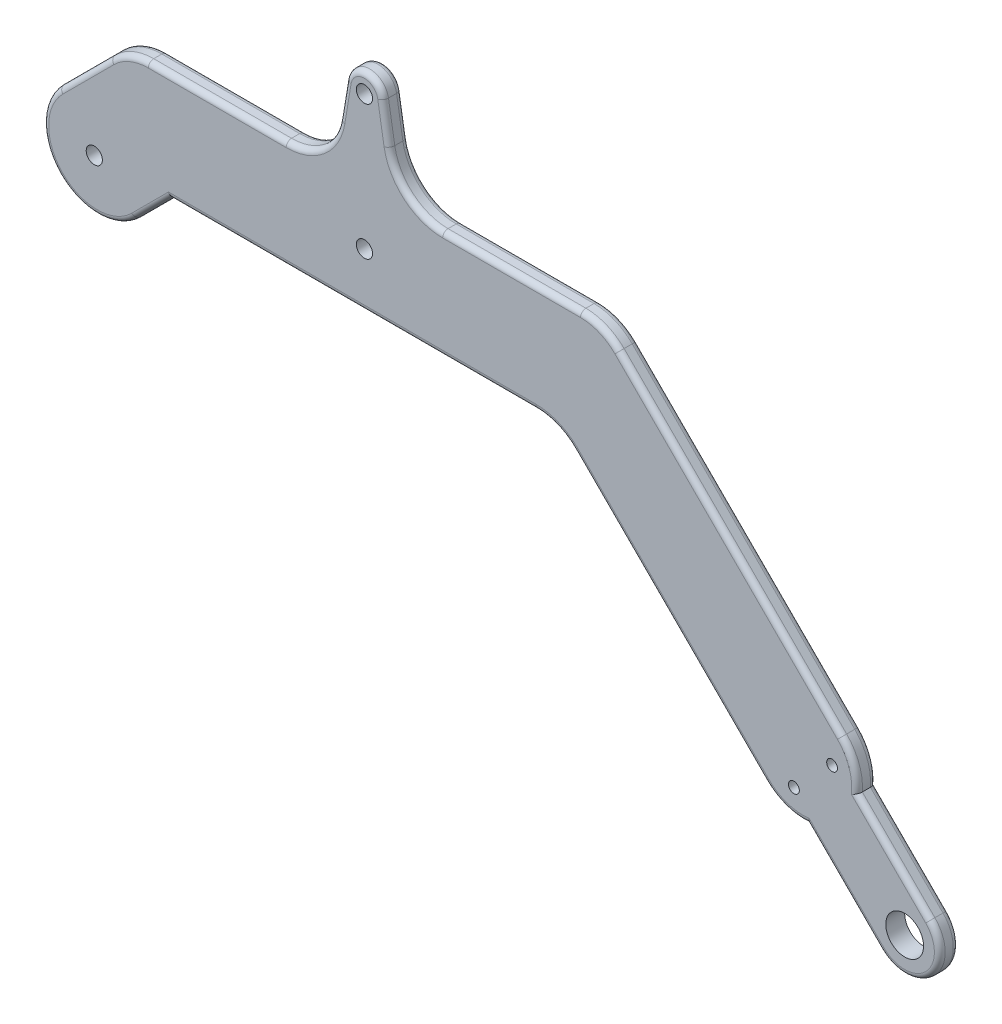
SolidWorks part; units mm, degrees
ref_plane "Front Plane" through (0, 0, 0) normal (0, 0, 1) x (1, 0, 0)
ref_plane "Top Plane" through (0, 0, 0) normal (0, 1, 0) x (1, 0, 0)
ref_plane "Right Plane" through (0, 0, 0) normal (1, 0, 0) x (0, 0, -1)
sketch "Sketch1" plane through (0, 0, 0) normal (0, 0, 1) x (1, 0, 0)
  line L0 (-100, 0) -> (100, 0) construction
  line L1 (-100, 0) -> (0, 100) construction
  line L2 (0, 100) -> (100, 0) construction
  line L3 (0, 0) -> (-50, 50) construction
  line L4 (-40, 60) -> (40, 60) construction
  line L5 (0, 100) -> (0, 60) construction
  circle A0 centre (-100, 0) radius 20
  circle A1 centre (0, 0) radius 20
  circle A2 centre (100, 0) radius 20
  point P2 (0, 0)
  dimension "D5" = 40
  dimension "D1" = 200
  dimension "D2" = 90
  dimension "D3" = 90
  dimension "D4" = 80
sketch "Sketch2" plane through (0, 0, 0) normal (0, 0, 1) x (1, 0, 0)
  line L0 (-56.5165, 43.4835) -> (-40, 60) construction
  line L1 (-100, 0) -> (0, 100) construction
  line L2 (-40, 60) -> (40, 60) construction
  line L3 (40, 60) -> (86.565, 13.435) construction
  line L4 (0, 100) -> (100, 0) construction
  line L5 (-49.4454, 36.4124) -> (-35.8579, 50)
  line L6 (-35.8579, 50) -> (35.8579, 50)
  line L7 (35.8579, 50) -> (79.4939, 6.364)
  line L8 (-63.5876, 50.5546) -> (-44.1421, 70)
  line L9 (-44.1421, 70) -> (44.1421, 70)
  line L10 (44.1421, 70) -> (93.636, 20.5061)
  line L11 (-63.5876, 50.5546) -> (-49.4454, 36.4124)
  line L12 (93.636, 20.5061) -> (79.4939, 6.364)
  line L13 (81.9688, 8.8388) -> (95.4038, -4.5962)
  line L14 (91.1612, 18.0312) -> (104.5962, 4.5962)
  line L15 (90.1005, 24.0416) -> (75.9584, 9.8995) construction
  line L16 (0, 100) -> (0, 60) construction
  line L17 (-6, 70) -> (-3.4532, 85.4203)
  line L18 (6, 70) -> (3.4532, 85.4203)
  circle A0 centre (100, 0) radius 10 construction
  circle A1 centre (100, 0) radius 3.5
  arc A2 (95.4038, -4.5962) -> (104.5962, 4.5962) centre (100, 0) ccw
  circle A3 centre (100, 0) radius 0.5
  circle A4 centre (100, 0) radius 6.5 construction
  circle A5 centre (79.4939, 13.435) radius 1
  circle A6 centre (86.565, 20.5061) radius 1
  circle A7 centre (0, 60) radius 1.5
  circle A8 centre (0, 84.85) radius 1.5
  circle A9 centre (0, 84.85) radius 3.5
  circle A10 centre (-50, 50) radius 1.5
  dimension "D4" = 20
  dimension "D5" = 7
  dimension "D12" = 2
  dimension "D13" = 3
  dimension "D18" = 3
  dimension "D3" = 27.5
  dimension "D8" = 19
  dimension "D9" = 5
  dimension "D10" = 5
  dimension "D11" = 5
  dimension "D14" = 14.85
  dimension "D16" = 6
  dimension "D17" = 6
  dimension "D1" = 10
  dimension "D2" = 10
  dimension "D6" = 3
  dimension "D7" = 3
  dimension "D15" = 2
sketch "Sketch3" plane through (0, 0, 0) normal (0, 0, 1) x (1, 0, 0)
  line L0 (-100, 0) -> (100, 0) construction
  line L1 (-86.565, 13.435) -> (-50, 50) construction
  line L2 (-100, 0) -> (0, 100) construction
  line L3 (-50, 50) -> (-13.435, 13.435) construction
  line L4 (0, 0) -> (-50, 50) construction
  line L5 (-79.4939, 6.364) -> (-50, 35.8579)
  line L6 (-50, 35.8579) -> (-20.5061, 6.364)
  line L7 (-93.636, 20.5061) -> (-50, 64.1421)
  line L8 (-50, 64.1421) -> (-6.364, 20.5061)
  line L9 (-93.636, 20.5061) -> (-79.4939, 6.364)
  line L10 (-20.5061, 6.364) -> (-6.364, 20.5061)
  line L11 (-91.1612, 18.0312) -> (-104.5962, 4.5962)
  line L12 (-81.9688, 8.8388) -> (-95.4038, -4.5962)
  line L13 (-18.0312, 8.8388) -> (-4.5962, -4.5962)
  line L14 (-8.8388, 18.0312) -> (4.5962, 4.5962)
  line L15 (-90.1005, 24.0416) -> (-75.9584, 9.8995) construction
  line L16 (-9.8995, 24.0416) -> (-24.0416, 9.8995) construction
  circle A0 centre (-100, 0) radius 3.5
  circle A1 centre (0, 0) radius 3.5
  circle A2 centre (-100, 0) radius 10 construction
  circle A3 centre (0, 0) radius 10 construction
  circle A4 centre (-100, 0) radius 6.5
  circle A5 centre (0, 0) radius 6.5
  circle A6 centre (-86.565, 20.5061) radius 1
  circle A7 centre (-79.4939, 13.435) radius 1
  circle A8 centre (-20.5061, 13.435) radius 1
  circle A9 centre (-13.435, 20.5061) radius 1
  circle A10 centre (-50, 50) radius 1.5 construction
  circle A11 centre (-50, 50) radius 1.5
  dimension "D1" = 20
  dimension "D2" = 7
  dimension "D8" = 2
  dimension "D11" = 5
  dimension "D12" = 5
  dimension "D13" = 5
  dimension "D14" = 5
  dimension "D6" = 19
  dimension "D7" = 19
  dimension "D9" = 5
  dimension "D10" = 5
  dimension "D3" = 3
  dimension "D4" = 10
  dimension "D5" = 10
sketch "Sketch4" plane through (0, 0, 0) normal (0, 0, 1) x (1, 0, 0)
  line L0 (-44.1421, 70) -> (44.1421, 70)
  line L1 (44.1421, 70) -> (57.5, 84.85)
  line L2 (57.5, 84.85) -> (57.5, 94.85)
  line L3 (57.5, 94.85) -> (-57.5, 94.85)
  line L4 (-57.5, 94.85) -> (-57.5, 84.85)
  line L5 (-57.5, 84.85) -> (-44.1421, 70)
  line L6 (-4, 60) -> (-4, 70)
  line L7 (4, 60) -> (4, 70)
  line L8 (-22.5, 86.35) -> (22.5, 86.35) construction
  line L9 (-22.5, 90.85) -> (22.5, 90.85)
  line L10 (-22.5, 81.85) -> (22.5, 81.85)
  circle A0 centre (0, 60) radius 1.5 construction
  circle A1 centre (0, 60) radius 1.5
  arc A2 (-4, 60) -> (4, 60) centre (0, 60) ccw
  circle A3 centre (0, 60) radius 4 construction
  arc A4 (-22.5, 90.85) -> (-22.5, 81.85) centre (-22.5, 86.35) ccw
  arc A5 (22.5, 81.85) -> (22.5, 90.85) centre (22.5, 86.35) ccw
  point P4 (0, 94.85)
  point P22 (0, 86.35)
  dimension "D1" = 115
  dimension "D2" = 10
  dimension "D3" = 2.5
  dimension "D4" = 45
  dimension "D5" = 9
  dimension "D6" = 4
sketch "Sketch5" plane through (0, 0, 0) normal (0, 0, 1) x (1, 0, 0)
  line L0 (81.9688, 8.8388) -> (95.4038, -4.5962) construction
  line L1 (91.1612, 18.0312) -> (104.5962, 4.5962) construction
  line L2 (6, 70) -> (3.4532, 85.4203) construction
  line L3 (-6, 70) -> (-3.4532, 85.4203) construction
  line L4 (81.9688, 8.8388) -> (95.4038, -4.5962)
  line L5 (91.1612, 18.0312) -> (104.5962, 4.5962)
  line L6 (6, 70) -> (3.4532, 85.4203)
  line L7 (-6, 70) -> (-3.4532, 85.4203)
  line L8 (93.636, 20.5061) -> (44.1421, 70)
  line L9 (79.4939, 6.364) -> (93.636, 20.5061)
  line L10 (35.8579, 50) -> (79.4939, 6.364)
  line L11 (-35.8579, 50) -> (35.8579, 50)
  line L12 (-49.4454, 36.4124) -> (-35.8579, 50)
  line L13 (-63.5876, 50.5546) -> (-49.4454, 36.4124)
  line L14 (-44.1421, 70) -> (-63.5876, 50.5546)
  line L15 (44.1421, 70) -> (-44.1421, 70)
  line L16 (93.636, 20.5061) -> (44.1421, 70)
  line L17 (79.4939, 6.364) -> (81.9688, 8.8388)
  line L18 (35.8579, 50) -> (79.4939, 6.364)
  line L19 (-35.8579, 50) -> (35.8579, 50)
  line L20 (-49.4454, 36.4124) -> (-35.8579, 50)
  line L21 (-63.5876, 50.5546) -> (-49.4454, 36.4124)
  line L22 (-44.1421, 70) -> (-63.5876, 50.5546)
  line L23 (44.1421, 70) -> (6, 70)
  line L24 (-6, 70) -> (-44.1421, 70)
  line L25 (91.1612, 18.0312) -> (93.636, 20.5061)
  arc A0 (95.4038, -4.5962) -> (104.5962, 4.5962) centre (100, 0) ccw construction
  circle A1 centre (79.4939, 13.435) radius 1
  circle A2 centre (79.4939, 13.435) radius 1
  circle A3 centre (100, 0) radius 0.5
  circle A4 centre (100, 0) radius 0.5
  circle A5 centre (100, 0) radius 3.5
  circle A6 centre (100, 0) radius 3.5
  circle A7 centre (0, 84.85) radius 3.5
  arc A8 (3.4532, 85.4203) -> (-3.4532, 85.4203) centre (0, 84.85) ccw
  circle A9 centre (0, 84.85) radius 1.5
  circle A10 centre (0, 84.85) radius 1.5
  circle A11 centre (0, 60) radius 1.5
  circle A12 centre (0, 60) radius 1.5
  circle A13 centre (86.565, 20.5061) radius 1
  circle A14 centre (86.565, 20.5061) radius 1
  circle A15 centre (-50, 50) radius 1.5
  circle A16 centre (-50, 50) radius 1.5
  arc A17 (95.4038, -4.5962) -> (104.5962, 4.5962) centre (100, 0) ccw
  dimension "D1" = 0
  dimension "D2" = 0
  dimension "D3" = 0
  dimension "D4" = 0
  dimension "D5" = 0
  dimension "D6" = 0
  dimension "D7" = 0
  dimension "D8" = 0
  dimension "D9" = 0
extrude "Boss-Extrude1" add sketch "Sketch5" along normal blind 3.5 contours L4 A17 L5 L25 L16 L23 L6 A8 L7 L24 L22 L21 L20 L19 L18 L17 A2 A6 A10 A12 A14 A16 region at (94.4348, 5.5652, 0) region at (18.0255, 50.1428, 0) region at (0, 75.758, 0) region at (3.3896, 85.128, 0)
fillet "Fillet1" radius 10 9 edges at (79.4939, 6.364, 1.75) (93.636, 20.5061, 1.75) (35.8579, 50, 1.75) (44.1421, 70, 1.75) (6, 70, 1.75) (-6, 70, 1.75) (-44.1421, 70, 1.75) (-49.4454, 36.4124, 1.75) (-63.5876, 50.5546, 1.75)
fillet "Fillet2" radius 1 44 edges at (97.8787, 11.3137, 0) (104.5962, -4.5962, 0) (77.7268, 9.4279, 0) (56.4536, 29.4043, 0) (35.5426, 49.2388, 0) (90.5721, 22.2732, 0) (67.6668, 46.4754, 0) (43.8268, 69.2388, 0) (27.2419, 70, 0) (8.0145, 72.3745, 0) (4.0354, 81.8954, 0) (-39.1161, 46.7417, 0) (-49.4454, 40.5546, 0) (-59.4454, 50.5546, 0) (-51.7938, 62.3483, 0) (-43.8268, 69.2388, 0) (-27.2419, 70, 0) (-8.0145, 72.3745, 0) (-4.0354, 81.8954, 0) (97.8787, 11.3137, 3.5) (104.5962, -4.5962, 3.5) (77.7268, 9.4279, 3.5) (56.4536, 29.4043, 3.5) (35.5426, 49.2388, 3.5) (90.5721, 22.2732, 3.5) (67.6668, 46.4754, 3.5) (43.8268, 69.2388, 3.5) (27.2419, 70, 3.5) (8.0145, 72.3745, 3.5) (4.0354, 81.8954, 3.5) (0, 88.35, 3.5) (-4.0354, 81.8954, 3.5) (-8.0145, 72.3745, 3.5) (-27.2419, 70, 3.5) (-43.8268, 69.2388, 3.5) (-39.1161, 46.7417, 3.5) (-49.4454, 40.5546, 3.5) (-59.4454, 50.5546, 3.5) (88.6863, 2.1213, 0) (-2.0711, 50, 0) (0, 88.35, 0) (88.6863, 2.1213, 3.5) (-2.0711, 50, 3.5) (-51.7938, 62.3483, 3.5)
scale "Scale1" scale about centroid uniform scaling yes scale factor 18
